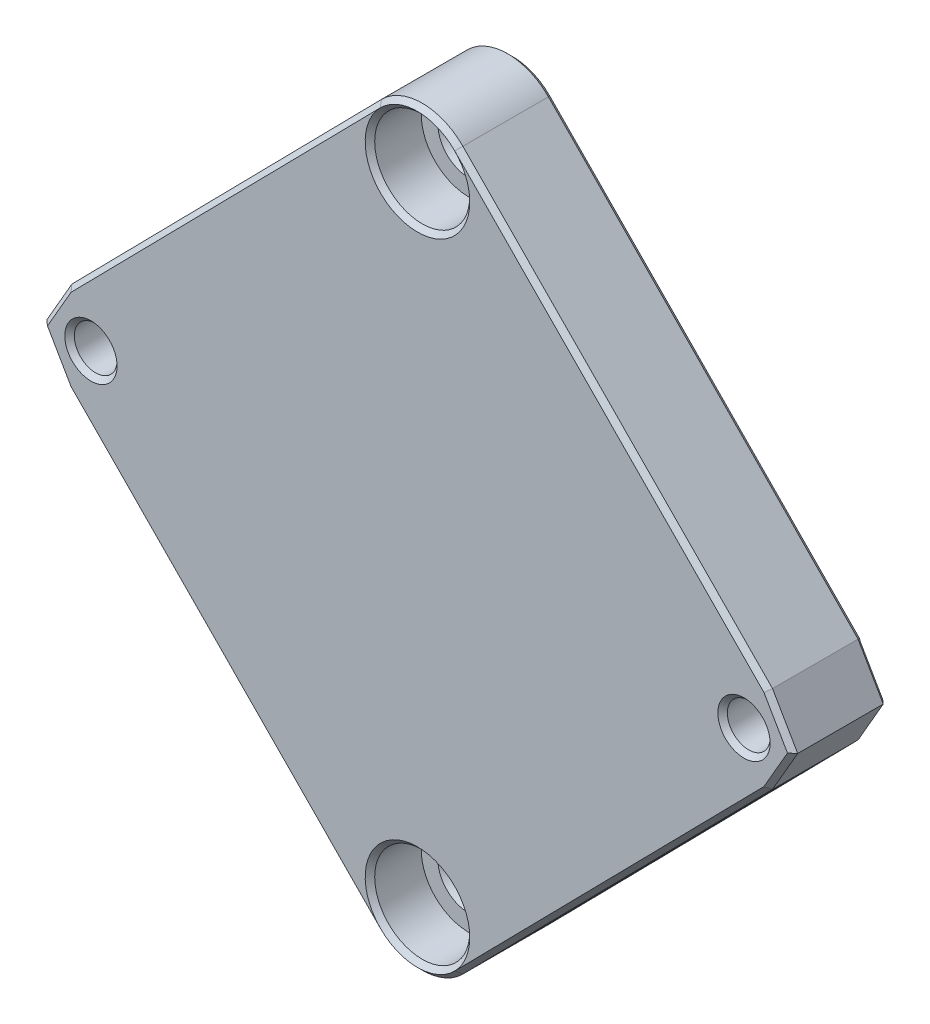
SolidWorks part; units mm, degrees
ref_plane "Top" through (0, 0, 0) normal (0, 0, 1) x (1, 0, 0)
ref_plane "Front" through (0, 0, 0) normal (0, 1, 0) x (1, 0, 0)
ref_plane "Right" through (0, 0, 0) normal (1, 0, 0) x (0, 0, -1)
sketch "Sketch1" plane through (0, 0, 0) normal (0, 0, 1) x (1, 0, 0)
  line L1 (0, 0) -> (79, 0)
  line L2 (0, 0) -> (0, 87)
  line L3 (0, 87) -> (79, 87)
  line L4 (79, 0) -> (79, 87)
  dimension "D1" = 79
  dimension "D2" = 87
extrude "Boss-Extrude1" add sketch "Sketch1" along normal blind 10
sketch "Sketch4" plane through (0, 0, 10) normal (0, 0, 1) x (1, 0, 0)
  line L0 (5.15, 43.5) -> (73.85, 43.5)
  line L2 (79, 0) -> (79, 87) construction
  line L5 (79, 87) -> (0, 87) construction
  point P2 (39.5, 43.5)
  dimension "D1" = 68.7
  dimension "D2" = 39.5
  dimension "D3" = 43.5
hole_wizard "M4 Clearance Hole1" positions "Sketch5" profile "Sketch6" hole size "M4" standard "DIN" end condition through all
sketch "Sketch5" plane through (0, 0, 10) normal (0, 0, 1) x (1, 0, 0)
  point P0 (5.15, 43.5)
  point P3 (73.85, 43.5)
sketch "Sketch6" plane through (5.15, 43.5, 10) normal (1, 0, 0) x (0, -1, 0)
  line L0 (0, 0) -> (0, 10)
  line L1 (0, 10) -> (2.25, 10)
  line L2 (2.25, 10) -> (2.25, 0)
  line L5 (2.25, 0) -> (0, 0)
  line L11 (0, -6.35) -> (0, 107.95) construction
  dimension "Thru Hole Dia." = 4.5
  dimension "Thru Hole Depth" = 10
sketch "Sketch11" plane through (0, 0, 0) normal (0, 0, -1) x (-1, 0, 0)
  line L0 (-79, 87) -> (0, 87) construction
  line L1 (-69.6353, 43.5) -> (-71.7427, 47.15)
  line L2 (-71.7427, 47.15) -> (-75.9573, 47.15)
  line L3 (-75.9573, 47.15) -> (-78.0647, 43.5)
  line L4 (-78.0647, 43.5) -> (-75.9573, 39.85)
  line L5 (-75.9573, 39.85) -> (-71.7427, 39.85)
  line L6 (-71.7427, 39.85) -> (-69.6353, 43.5)
  line L7 (-9.3647, 43.5) -> (-7.2573, 39.85)
  line L8 (-7.2573, 39.85) -> (-3.0427, 39.85)
  line L9 (-3.0427, 39.85) -> (-0.9353, 43.5)
  line L10 (-0.9353, 43.5) -> (-3.0427, 47.15)
  line L11 (-3.0427, 47.15) -> (-7.2573, 47.15)
  line L12 (-7.2573, 47.15) -> (-9.3647, 43.5)
  circle A0 centre (-73.85, 43.5) radius 3.65 construction
  circle A1 centre (-5.15, 43.5) radius 3.65 construction
  dimension "D1" = 7.3
  dimension "D2" = 7.3
extrude "Cut-Extrude3" cut sketch "Sketch11" against normal blind 3.5
sketch "Sketch12" plane through (0, 0, 10) normal (0, 0, -1) x (-1, 0, 0)
  line L0 (-39.5, 77) -> (-39.5, 10)
  line L1 (-79, 0) -> (-79, 87) construction
  line L3 (-79, 87) -> (0, 87) construction
  dimension "D1" = 39.5
  dimension "D2" = 67
  dimension "D3" = 10
hole_wizard "CBORE for M5 Socket Head Cap Screw1" positions "Sketch15" profile "Sketch16" counterbore size "M5" standard "DIN" end condition through all
sketch "Sketch15" plane through (0, 0, 10) normal (0, 0, 1) x (1, 0, 0)
  point P0 (39.5, 77)
  point P3 (39.5, 10)
sketch "Sketch16" plane through (39.5, 77, 10) normal (1, 0, 0) x (0, -1, 0)
  line L0 (0, 0) -> (0, 10)
  line L1 (0, 10) -> (2.75, 10)
  line L3 (2.75, 10) -> (2.75, 5.4)
  line L4 (2.75, 5.4) -> (5, 5.4)
  line L5 (5, 5.4) -> (5, 0)
  line L7 (5, 0) -> (0, 0)
  line L11 (0, -6.35) -> (0, 107.95) construction
  dimension "Thru Hole Dia." = 5.5
  dimension "Thru Hole Depth" = 10
  dimension "C'Bore Dia." = 10
  dimension "C'Bore Depth" = 5.4
sketch "Sketch17" plane through (0, 0, 0) normal (0, 0, -1) x (-1, 0, 0)
  line L0 (-76.3481, 48.0932) -> (-43.7776, 81.2074)
  line L2 (-35.2224, 81.2074) -> (-2.6519, 48.0932)
  line L4 (-76.3481, 38.9068) -> (-43.7776, 5.7926)
  line L5 (-35.2224, 5.7926) -> (-2.6519, 38.9068)
  line L14 (-2.6519, 38.9068) -> (0, 43.5)
  line L15 (0, 87) -> (0, 0) construction
  line L16 (0, 43.5) -> (-2.6519, 48.0932)
  line L17 (-0.9353, 43.5) -> (-3.0427, 47.15) construction
  line L18 (-3.0427, 39.85) -> (-0.9353, 43.5) construction
  line L20 (-76.3481, 48.0932) -> (-79, 43.5)
  line L21 (-79, 0) -> (-79, 87) construction
  line L22 (-79, 43.5) -> (-76.3481, 38.9068)
  line L23 (-78.0647, 43.5) -> (-75.9573, 39.85) construction
  line L24 (-75.9573, 47.15) -> (-78.0647, 43.5) construction
  line L25 (-125.188, 43.5) -> (-108.4403, 14.492)
  line L26 (-108.4403, 14.492) -> (-72.295, -22.2566)
  line L27 (-6.705, -22.2566) -> (29.4403, 14.492)
  line L28 (29.4403, 14.492) -> (46.188, 43.5)
  line L29 (46.188, 43.5) -> (29.4403, 72.508)
  line L30 (-6.705, 109.2566) -> (29.4403, 72.508)
  line L31 (-108.4403, 72.508) -> (-72.295, 109.2566)
  line L32 (-108.4403, 72.508) -> (-125.188, 43.5)
  arc A0 (-43.7776, 81.2074) -> (-35.2224, 81.2074) centre (-39.5, 77) cw
  arc A1 (-43.7776, 5.7926) -> (-35.2224, 5.7926) centre (-39.5, 10) ccw
  arc A4 (-72.295, -22.2566) -> (-6.705, -22.2566) centre (-39.5, 10) ccw
  arc A5 (-72.295, 109.2566) -> (-6.705, 109.2566) centre (-39.5, 77) cw
  dimension "D2" = 6
  dimension "D4" = 6
  dimension "D1" = 0.94
  dimension "D3" = 0.94
  dimension "D5" = 0.94
  dimension "D6" = 0.94
  dimension "D7" = 40
extrude "Cut-Extrude4" cut sketch "Sketch17" against normal blind 10
chamfer "Chamfer1" distance 0.5 angle 45 38 edges at (77.6741, 41.2034, 10) (60.0629, 22.3497, 10) (39.5, 4, 10) (18.9371, 22.3497, 10) (1.3259, 41.2034, 10) (1.3259, 45.7966, 10) (18.9371, 64.6503, 10) (39.5, 83, 10) (60.0629, 64.6503, 10) (77.6741, 45.7966, 10) (76.1, 43.5, 10) (7.4, 43.5, 10) (44.5, 10, 10) (44.5, 77, 10) (39.5, 83, 0) (18.9371, 64.6503, 0) (1.3259, 45.7966, 0) (1.3259, 41.2034, 0) (18.9371, 22.3497, 0) (39.5, 4, 0) (60.0629, 22.3497, 0) (77.6741, 41.2034, 0) (77.6741, 45.7966, 0) (60.0629, 64.6503, 0) (8.311, 41.675, 0) (5.15, 39.85, 0) (1.989, 41.675, 0) (1.989, 45.325, 0) (5.15, 47.15, 0) (8.311, 45.325, 0) (70.689, 45.325, 0) (73.85, 47.15, 0) (77.011, 45.325, 0) (77.011, 41.675, 0) (73.85, 39.85, 0) (70.689, 41.675, 0) (42.25, 10, 0) (42.25, 77, 0)
chamfer "Chamfer2" distance 0.5 angle 45 2 edges at (42.25, 10, 4.6) (42.25, 77, 4.6)
